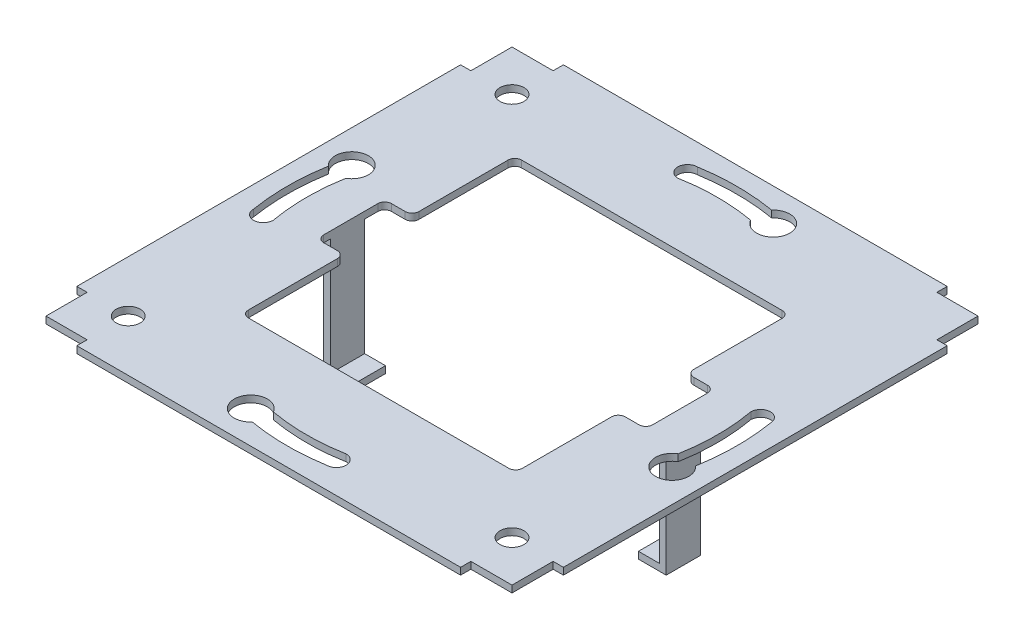
SolidWorks part; units mm, degrees
ref_plane "Спереди" through (0, 0, 0) normal (0, 0, 1) x (1, 0, 0)
ref_plane "Сверху" through (0, 0, 0) normal (0, 1, 0) x (1, 0, 0)
ref_plane "Справа" through (0, 0, 0) normal (1, 0, 0) x (0, 0, -1)
sketch "Эскиз2" plane through (0, 0, 0) normal (0, 1, 0) x (1, 0, 0)
  line L0 (-35.5, 28) -> (-35.5, -28)
  line L1 (28, -35.5) -> (-28, -35.5)
  line L3 (28, 35.5) -> (-28, 35.5)
  line L5 (28, -35.5) -> (-28, 35.5) construction
  line L6 (28, 35.5) -> (-28, -35.5) construction
  line L7 (35.5, 28) -> (35.5, -28)
  line L8 (-34, 34) -> (-28, 34)
  line L9 (28, 34) -> (34, 34)
  line L10 (34, 28) -> (34, 34)
  line L11 (34, -28) -> (34, -34)
  line L12 (28, -34) -> (34, -34)
  line L13 (-34, -34) -> (-28, -34)
  line L14 (-34, -28) -> (-34, -34)
  line L15 (-34, 28) -> (-34, 34)
  line L16 (28, 34) -> (28, 35.5)
  line L17 (34, 28) -> (35.5, 28)
  line L18 (34, -28) -> (35.5, -28)
  line L19 (28, -35.5) -> (28, -34)
  line L20 (-28, -34) -> (-28, -35.5)
  line L21 (-35.5, -28) -> (-34, -28)
  line L22 (-35.5, 28) -> (-34, 28)
  line L23 (-28, 35.5) -> (-28, 34)
  line L24 (20, 19.4181) -> (20, 6.5255)
  line L25 (-19, 20.4181) -> (19, 20.4181)
  line L27 (-19, -19.4745) -> (19, -19.4745)
  line L29 (20, -18.4745) -> (20, -5.4745)
  line L30 (21, 5.5255) -> (23, 5.5255)
  line L31 (21, -4.4745) -> (23, -4.4745)
  line L32 (24, 4.5255) -> (24, -3.4745)
  line L33 (-20, 19.4181) -> (-20, 6.4181)
  line L34 (-20, -18.4745) -> (-20, -5.4745)
  line L35 (-21, -4.4745) -> (-23, -4.4745)
  line L36 (-24, -3.4745) -> (-24, 4.4181)
  line L37 (-23, 5.4181) -> (-21, 5.4181)
  line L38 (0, 0) -> (-29.5317, 5.2802) construction
  line L39 (0, 0) -> (5.2802, 29.5317) construction
  line L40 (0, 0) -> (28, -28) construction
  line L41 (0, 0) -> (-28, -28) construction
  arc A0 (19, -19.4745) -> (20, -18.4745) centre (19, -18.4745) ccw
  arc A1 (19, 20.4181) -> (20, 19.4181) centre (19, 19.4181) cw
  arc A2 (-19, 20.4181) -> (-20, 19.4181) centre (-19, 19.4181) ccw
  arc A3 (-20, -18.4745) -> (-19, -19.4745) centre (-19, -18.4745) ccw
  arc A4 (-20, 6.4181) -> (-21, 5.4181) centre (-21, 6.4181) cw
  arc A5 (-20, -5.4745) -> (-21, -4.4745) centre (-21, -5.4745) ccw
  arc A6 (20, -5.4745) -> (21, -4.4745) centre (21, -5.4745) cw
  arc A7 (20, 6.5255) -> (21, 5.5255) centre (21, 6.5255) ccw
  arc A8 (-24, 4.4181) -> (-23, 5.4181) centre (-23, 4.4181) cw
  arc A9 (-23, -4.4745) -> (-24, -3.4745) centre (-23, -3.4745) cw
  arc A10 (23, -4.4745) -> (24, -3.4745) centre (23, -3.4745) ccw
  arc A11 (23, 5.5255) -> (24, 4.5255) centre (23, 4.5255) cw
  arc A12 (-32.3752, -5.3289) -> (-32.3375, 5.5534) centre (0, 0) cw
  arc A13 (-29.5229, -5.3289) -> (-29.5317, 5.2802) centre (0, 0) cw
  arc A15 (-32.3375, 5.5534) -> (-29.5317, 5.2802) centre (-30.7442, 7.3717) cw
  arc A16 (-32.3752, -5.3289) -> (-29.5229, -5.3289) centre (-30.9491, -5.3289) ccw
  arc A17 (5.5534, 32.3375) -> (5.2802, 29.5317) centre (7.3717, 30.7442) cw
  arc A18 (-5.3289, 32.3752) -> (5.5534, 32.3375) centre (0, 0) cw
  arc A19 (-5.3289, 29.5229) -> (5.2802, 29.5317) centre (0, 0) cw
  arc A20 (-5.3289, 32.3752) -> (-5.3289, 29.5229) centre (-5.3289, 30.9491) ccw
  arc A21 (32.3375, -5.5534) -> (29.5317, -5.2802) centre (30.7442, -7.3717) cw
  arc A22 (32.3752, 5.3289) -> (32.3375, -5.5534) centre (0, 0) cw
  arc A23 (29.5229, 5.3289) -> (29.5317, -5.2802) centre (0, 0) cw
  arc A24 (32.3752, 5.3289) -> (29.5229, 5.3289) centre (30.9491, 5.3289) ccw
  arc A25 (-5.5534, -32.3375) -> (-5.2802, -29.5317) centre (-7.3717, -30.7442) cw
  arc A26 (5.3289, -32.3752) -> (-5.5534, -32.3375) centre (0, 0) cw
  arc A27 (5.3289, -29.5229) -> (-5.2802, -29.5317) centre (0, 0) cw
  arc A28 (5.3289, -32.3752) -> (5.3289, -29.5229) centre (5.3289, -30.9491) ccw
  circle A29 centre (28, -28) radius 1.75
  circle A32 centre (-28, -28) radius 1.75
  circle A33 centre (-28, 28) radius 1.75
  point P0 (0, 0)
  point P40 (20, -19.4745)
  point P43 (20, 20.4181)
  point P46 (-20, 20.4181)
  point P49 (-20, -19.4745)
  point P52 (-20, 5.4181)
  point P59 (20, 5.5255)
  dimension "D1" = 1
  dimension "D4" = 3
  dimension "D3" = 90
  dimension "D5" = 90
  dimension "D2" = 4
extrude "Бобышка-Вытянуть1" add sketch "Эскиз2" along normal blind 1
sketch "Эскиз3" plane through (0, 0, 0) normal (0, 0, 1) x (1, 0, 0)
  line L0 (-25, 0) -> (-24, 0)
  line L2 (-24, 0) -> (-24, -17)
  line L3 (-24, -17) -> (-20.9534, -17)
  line L4 (-20.9534, -17) -> (-20.9534, -18)
  line L5 (-20.9534, -18) -> (-25, -18)
  line L6 (-25, 0) -> (-25, -18)
  line L8 (0, 16.6146) -> (0, -8.6072) construction
  line L9 (25, 0) -> (25, -18)
  line L10 (20.9534, -18) -> (25, -18)
  line L11 (20.9534, -17) -> (20.9534, -18)
  line L12 (24, -17) -> (20.9534, -17)
  line L13 (24, 0) -> (24, -17)
  line L14 (25, 0) -> (24, 0)
  line L15 (-28, 0) -> (28, 0) construction
extrude "Бобышка-Вытянуть2" add sketch "Эскиз3" along normal mid plane 5
